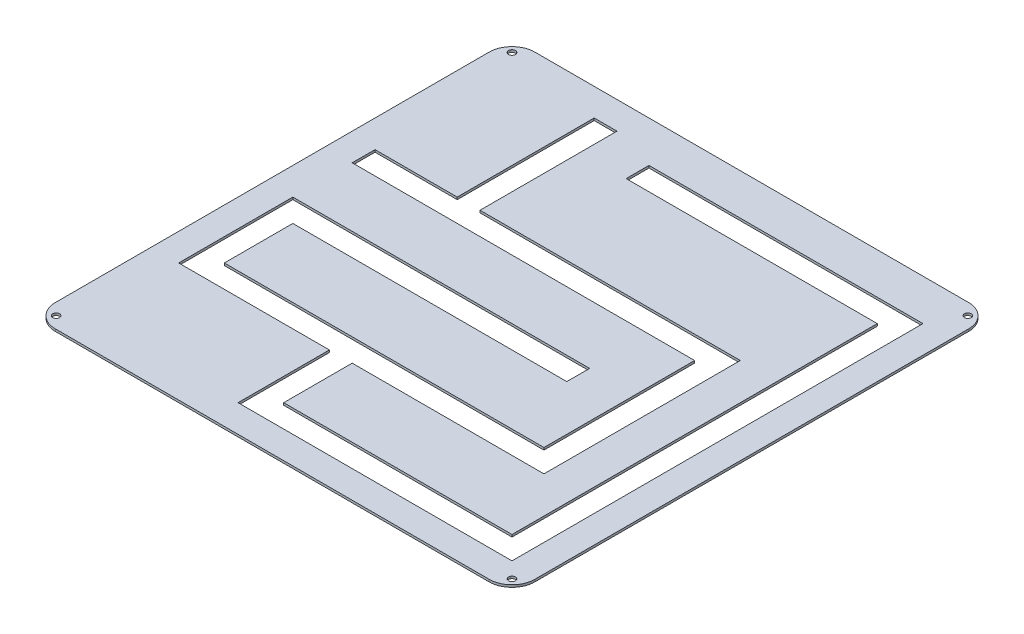
SolidWorks part; units mm, degrees
ref_plane "Front Plane" through (0, 0, 0) normal (0, 0, 1) x (1, 0, 0)
ref_plane "Top Plane" through (0, 0, 0) normal (0, 1, 0) x (1, 0, 0)
ref_plane "Right Plane" through (0, 0, 0) normal (1, 0, 0) x (0, 0, -1)
sketch "Sketch1" plane through (0, 0, 0) normal (0, 1, 0) x (1, 0, 0)
  line L0 (-101, -101) -> (-101, 101)
  line L5 (-105, -105) -> (105, -105)
  line L6 (-105, -105) -> (-105, 105)
  line L7 (-105, 105) -> (105, 105)
  line L8 (105, -105) -> (105, 105)
  line L9 (-101, 101) -> (101, 101)
  line L10 (101, -101) -> (101, 101)
  line L11 (-101, -101) -> (101, -101)
  line L12 (-101, 101) -> (-99.8333, 99.8333) construction
  line L13 (-55, 0) -> (55, 0) construction
  line L14 (-101, -101) -> (-99.8333, -99.8333) construction
  line L15 (0, -55) -> (0, 55) construction
  line L16 (101, -101) -> (99.8333, -99.8333) construction
  line L17 (101, 101) -> (99.8333, 99.8333) construction
  circle A1 centre (-99.8333, 99.8333) radius 1.5
  circle A2 centre (-99.8333, -99.8333) radius 1.5
  circle A3 centre (99.8333, -99.8333) radius 1.5
  circle A4 centre (99.8333, 99.8333) radius 1.5
  point P0 (0, 0)
  point P6 (-105, 0)
  point P7 (0, 105)
  dimension "D3" = 4
  dimension "D4" = 3
  dimension "D1" = 210
  dimension "D2" = 210
  dimension "D5" = 1.65
  dimension "D6" = 45
extrude "MainExtrude" add sketch "Sketch1" along normal blind 1 contours L6 L5 L8 L7
extrude "ScrewHoles" cut sketch "Sketch1<6>" along normal up to surface (1 mm away) contours A1 | A2 | A3 | A4 up to face at (0, 1, 0)
sketch "Sketch1<6>" plane through (0, 0, 0) normal (0, 1, 0) x (1, 0, 0) same geometry as "Sketch1"
fillet "RoundedCorners" radius 10 4 edges at (-105, 0.5, -105) (-105, 0.5, 105) (105, 0.5, -105) (105, 0.5, 105)
sketch "Sketch3" plane through (0, 0, 0) normal (0, 1, 0) x (1, 0, 0)
  line L24 (-52, 93) -> (-52, 33) construction
  line L25 (-57, 93) -> (-57, 33)
  line L58 (-93, 28) -> (62, 28) construction
  line L59 (62, 28) -> (62, -48) construction
  line L60 (62, -48) -> (-88, -48) construction
  line L61 (-88, -48) -> (-88, -8) construction
  line L62 (-88, -8) -> (37, -8) construction
  line L63 (-22, -53) -> (-22, -88) construction
  line L64 (-22, -88) -> (88, -88) construction
  line L65 (88, -88) -> (88, 82) construction
  line L66 (88, 82) -> (-27, 82) construction
  line L68 (-93, 23) -> (57, 23)
  line L69 (57, 23) -> (57, -43)
  line L70 (57, -43) -> (-83, -43)
  line L71 (-83, -43) -> (-83, -13)
  line L72 (-83, -13) -> (37, -13)
  line L73 (-27, -53) -> (-27, -93)
  line L74 (-27, -93) -> (93, -93)
  line L75 (93, -93) -> (93, 87)
  line L76 (93, 87) -> (-27, 87)
  line L77 (-47, 93) -> (-47, 33)
  line L78 (-93, 33) -> (-57, 33)
  line L79 (67, 33) -> (67, -53)
  line L80 (67, -53) -> (-17, -53)
  line L81 (-93, -53) -> (-93, -3)
  line L82 (-93, -3) -> (37, -3)
  line L83 (-17, -53) -> (-17, -83)
  line L84 (-17, -83) -> (83, -83)
  line L85 (83, -83) -> (83, 77)
  line L86 (83, 77) -> (-27, 77)
  line L87 (-57, 93) -> (-47, 93)
  line L89 (-93, 23) -> (-93, 33)
  line L90 (37, -13) -> (37, -3)
  line L92 (-27, 87) -> (-27, 77)
  line L93 (-47, 93) -> (-47, 31.8434) construction
  line L94 (-52, 93) -> (-52, 31.8434) construction
  line L95 (-57, 93) -> (-57, 31.8434) construction
  line L96 (-17, 9.5948) -> (-17, -83) construction
  line L97 (-22, 9.5948) -> (-22, -88) construction
  line L98 (-27, 9.5948) -> (-27, -93) construction
  line L99 (-27, -53) -> (-93, -53)
  line L100 (67, -53) -> (-93, -53) construction
  line L101 (-47, 33) -> (67, 33)
  line L102 (-93, 33) -> (67, 33) construction
  line L106 (-105, -95) -> (-105, 95) construction
  line L107 (-95, -105) -> (95, -105) construction
  line L108 (-95, 105) -> (95, 105) construction
  line L109 (105, -95) -> (105, 95) construction
  dimension "D1" = 5
  dimension "D2" = 5
  dimension "D3" = 12
  dimension "D4" = 12
  dimension "D5" = 12
  dimension "D6" = 12
  dimension "D7" = 60
  dimension "D8" = 160
  dimension "D9" = 130
  dimension "D11" = 120
  dimension "D13" = 30
  dimension "D14" = 120
  dimension "D10" = 30
  dimension "D12" = 160
  dimension "D15" = 20
  dimension "D17" = 160
  dimension "D16" = 66
extrude "Trench" cut sketch "Sketch3" along normal blind 12
